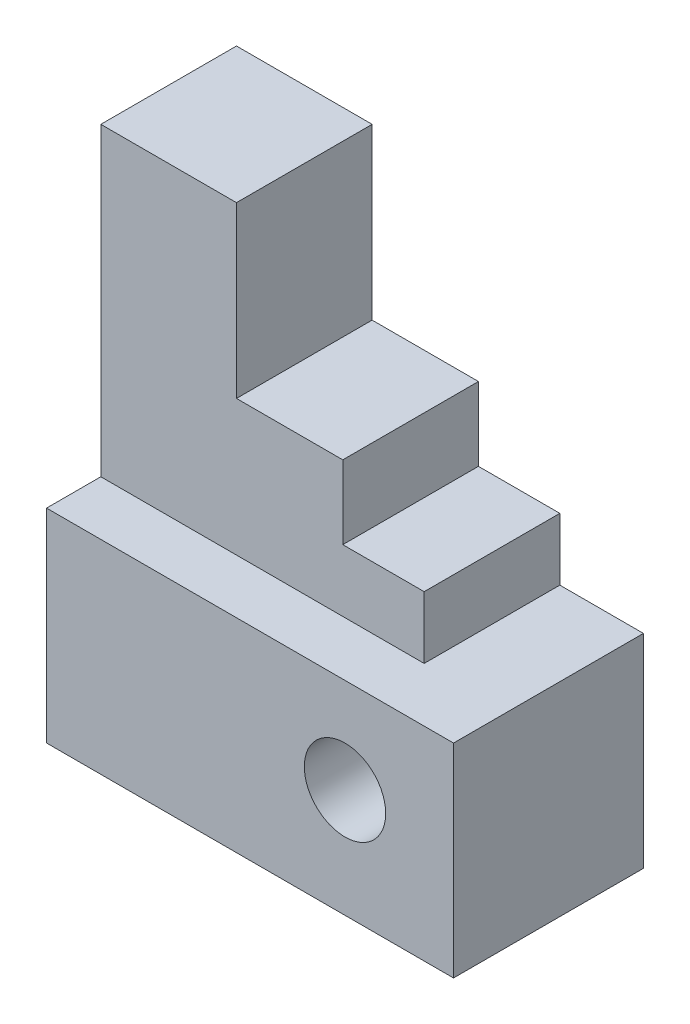
SolidWorks part; units mm, degrees
ref_plane "Front Plane" through (0, 0, 0) normal (0, 0, 1) x (1, 0, 0)
ref_plane "Top Plane" through (0, 0, 0) normal (0, 1, 0) x (1, 0, 0)
ref_plane "Right Plane" through (0, 0, 0) normal (1, 0, 0) x (0, 0, -1)
sketch "Sketch2" plane through (0, 0, 0) normal (0, 0, 1) x (1, 0, 0)
  line L0 (35.6737, 50) -> (35.6737, 39.1666)
  line L1 (0, 0) -> (60, 0)
  line L2 (0, 0) -> (0, 30)
  line L3 (0, 30) -> (60, 30)
  line L4 (60, 0) -> (60, 30)
  line L5 (0, 30) -> (47.6737, 30)
  line L6 (0, 30) -> (0, 50)
  line L7 (20, 50) -> (35.6737, 50)
  line L8 (47.6737, 30) -> (47.6737, 39.1666)
  line L10 (0, 50) -> (0, 75)
  line L11 (0, 75) -> (20, 75)
  line L12 (20, 50) -> (20, 75)
  line L13 (35.6737, 39.1666) -> (47.6737, 39.1666)
  circle A1 centre (44, 16) radius 6
  point P7 (0, 0)
  dimension "D6" = 16
  dimension "D1" = 60
  dimension "D2" = 30
  dimension "D3" = 20
  dimension "D4" = 25
  dimension "D5" = 20
  dimension "D7" = 16
extrude "Boss-Extrude1" add sketch "Sketch2" along normal blind 28 contours L1 L4 L3 L2 A1 region at (29.0614, 14.933, 0)
extrude "Boss-Extrude2" add sketch "Sketch2<3>" along normal blind 20 contours L13 L0 L7 L12 L11 L10 L6 L3 L8 region at (16.8573, 48.0502, 0)
sketch "Sketch2<3>" plane through (0, 0, 0) normal (0, 0, 1) x (1, 0, 0) same geometry as "Sketch2"
